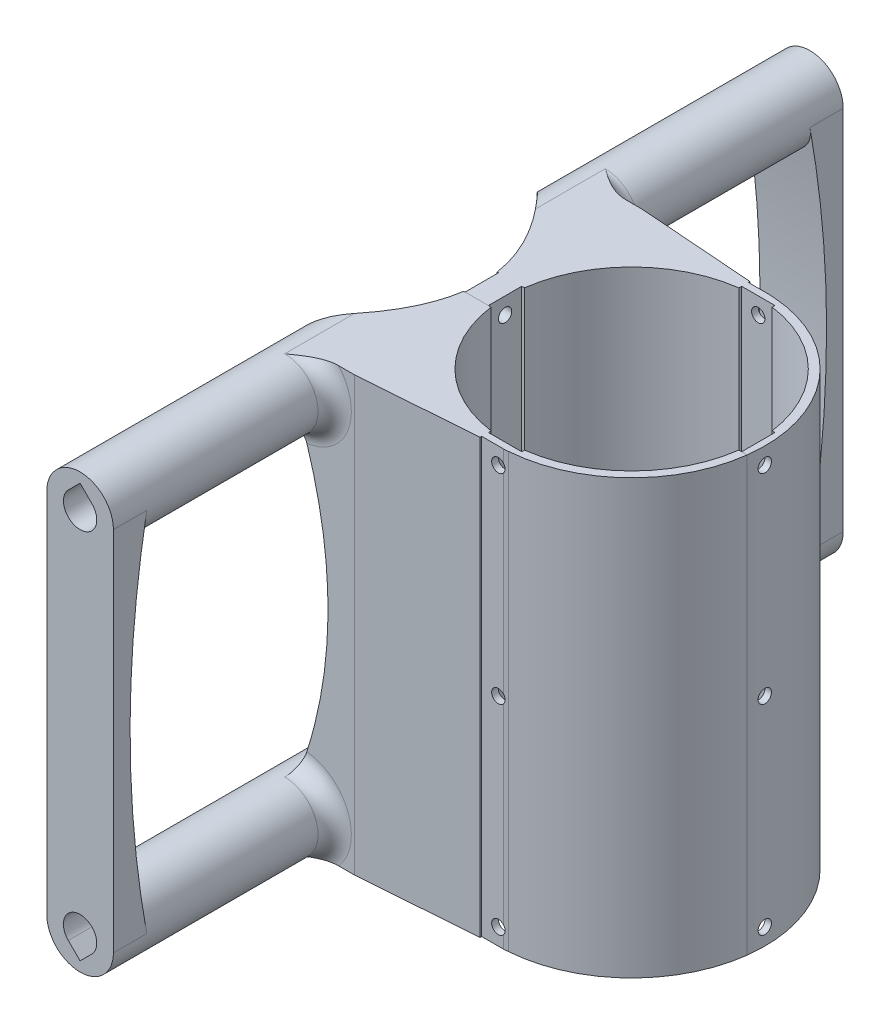
SolidWorks part; units mm, degrees
ref_plane "Front Plane" through (0, 0, 0) normal (0, 0, 1) x (1, 0, 0)
ref_plane "Top Plane" through (0, 0, 0) normal (0, 1, 0) x (1, 0, 0)
ref_plane "Right Plane" through (0, 0, 0) normal (1, 0, 0) x (0, 0, -1)
sketch "Sketch1" plane through (0, 0, 0) normal (0, 0, 1) x (1, 0, 0)
  line L4 (16, -10) -> (16, 10)
  line L5 (16, 100) -> (16, 10)
  line L6 (0, 100) -> (16, 55) construction
  line L7 (0, 120) -> (16, 120)
  line L10 (0, -10) -> (16, -10)
  line L12 (16, 55) -> (0, 10) construction
  line L14 (16, 100) -> (16, 120)
  circle A0 centre (0, 0) radius 4.7625
  circle A1 centre (0, 110) radius 4.7625
  arc A2 (0, 120) -> (0, 100) centre (0, 110) ccw
  arc A3 (0, 10) -> (0, -10) centre (0, 0) ccw
  spline S0 degree 2 poles (0, 100) (16, 55) (0, 10) knots 0 0 0 1 1 1
  point P5 (0, 55)
  dimension "D1" = 110
  dimension "D2" = 90
  dimension "D3" = 9.525
  dimension "D7" = 10
  dimension "D5" = 91.8619
  dimension "D6" = 10
  dimension "D4" = 20
  dimension "D8" = 65
  dimension "D9" = 16
extrude "Boss-Extrude1" add sketch "Sketch1" along normal blind 86.2 contours L4 A1 A0 region at (8, -8.6743, 0)
ref_plane "Plane3" through (0, 55, 0) normal (0, 1, 0) x (1, 0, 0)
sketch "Sketch3" plane through (0, 0, 0) normal (0, 1, 0) x (1, 0, 0)
  line L0 (16, 0) -> (58.9802, -3.2112)
  line L1 (16, -86.2) -> (58.9802, -82.9888)
  line L4 (16, 0) -> (16, -86.2)
  circle A1 centre (56, -43.1) radius 37.5
  arc A2 (58.9802, -82.9888) -> (58.9802, -3.2112) centre (56, -43.1) ccw
  dimension "D1" = 75
  dimension "D2" = 80
  dimension "D4" = 86.2
  dimension "D3" = 40
extrude "Boss-Extrude3" add sketch "Sketch3" along direction (0, 1, 0) on the side of the normal through all and the other way through all
sketch "Sketch9" plane through (0, 0, 86.2) normal (0, 0, 1) x (1, 0, 0)
  circle A0 centre (0, 110) radius 4.7625
  circle A1 centre (0, 110) radius 10
  circle A2 centre (0, 0) radius 10
  circle A3 centre (0, 0) radius 4.7625
  dimension "D1" = 9.525
  dimension "D2" = 20
  dimension "D4" = 110
  dimension "D3" = 2
extrude "Boss-Extrude5" add sketch "Sketch9" along normal blind 66.4 and the other way blind 152.6
sketch "Sketch4" plane through (0, 120, 0) normal (0, 1, 0) x (1, 0, 0)
  line L0 (-10, 66.4) -> (-10, -152.6) construction
  line L5 (-10, -5.6) -> (-10, -80.6)
  circle A2 centre (56, -43.1) radius 37.5 construction
  spline S0 degree 2 poles (-10, -80.6) (32, -43.1) (-10, -5.6) knots 0 0 0 1 1 1
  dimension "D2" = 21
  dimension "D4" = 37.5
  dimension "D3" = 45
  dimension "D1" = 75
extrude "Cut-Extrude1" cut sketch "Sketch4" against normal through all contours L5 S0 | S0 region at (-1.6, 120, 43.1)
ref_point "Point2"
sketch "Sketch7" plane through (0, 120, 0) normal (0, 1, 0) x (1, 0, 0)
  line L0 (51.0254, -81.1) -> (51.0254, -48.1)
  line L1 (51.0254, -81.1) -> (61.0254, -81.1)
  line L2 (51.0254, -5.1) -> (61.0254, -5.1)
  line L3 (61.0254, -81.1) -> (61.0254, -48.1)
  line L4 (51.0254, -81.1) -> (61.0254, -5.1) construction
  line L5 (51.0254, -5.1) -> (61.0254, -81.1) construction
  line L6 (18.0254, -48.1) -> (51.0254, -48.1)
  line L7 (18.0254, -48.1) -> (18.0254, -38.1)
  line L8 (94.0254, -48.1) -> (94.0254, -38.1)
  line L9 (18.0254, -38.1) -> (51.0254, -38.1)
  line L10 (18.0254, -48.1) -> (94.0254, -38.1) construction
  line L11 (94.0254, -48.1) -> (18.0254, -38.1) construction
  line L12 (61.0254, -38.1) -> (61.0254, -5.1)
  line L13 (61.0254, -48.1) -> (94.0254, -48.1)
  line L14 (51.0254, -38.1) -> (51.0254, -5.1)
  line L15 (61.0254, -38.1) -> (94.0254, -38.1)
  line L16 (61.0254, -83.1) -> (51.0254, -83.1)
  line L17 (96.0254, -38.1) -> (106.0254, -38.1)
  line L18 (96.0254, -38.1) -> (96.0254, -48.1)
  line L19 (96.0254, -48.1) -> (106.0254, -48.1)
  line L20 (106.0254, -38.1) -> (106.0254, -48.1)
  line L21 (61.0254, -83.1) -> (61.0254, -93.1)
  line L22 (61.0254, -93.1) -> (51.0254, -93.1)
  line L23 (51.0254, -83.1) -> (51.0254, -93.1)
  line L24 (11.0254, -48.1) -> (11.0254, -38.1)
  line L25 (11.0254, -48.1) -> (1.0254, -48.1)
  line L26 (1.0254, -48.1) -> (1.0254, -38.1)
  line L27 (11.0254, -38.1) -> (1.0254, -38.1)
  line L28 (51.0254, -3.1) -> (61.0254, -3.1)
  line L29 (51.0254, -3.1) -> (51.0254, 6.9)
  line L30 (51.0254, 6.9) -> (61.0254, 6.9)
  line L31 (61.0254, -3.1) -> (61.0254, 6.9)
  point P1 (56.0254, -43.1)
  point P2 (56.0254, -43.1)
  point P33 (56.0254, -43.1)
  dimension "D1" = 10
  dimension "D2" = 38
  dimension "D3" = 76
  dimension "D4" = 2
  dimension "D5" = 10
  dimension "D6" = 10
  dimension "D8" = 7
extrude "Cut-Extrude2" cut sketch "Sketch7" against normal through all
fillet "Fillet4" radius 5 4 edges at (10, 110, 0) (10, 0, 0) (10, 0, 86.2) (10, 110, 86.2)
ref_plane "Plane10" through (-10, 0, 0) normal (-1, 0, 0) x (0, 0, 1)
sketch "Sketch23" plane through (-10, 0, 0) normal (-1, 0, 0) x (0, 0, 1)
  line L0 (152.6, 110) -> (142.6, 110)
  line L1 (152.6, 100) -> (152.6, 120) construction
  line L2 (152.6, 0) -> (142.6, 0)
  line L3 (152.6, -10) -> (152.6, 10) construction
  line L4 (152.6, 110) -> (152.6, 0)
  line L5 (142.6, 110) -> (152.6, 55) construction
  line L6 (152.6, 55) -> (142.6, 0) construction
  spline S1 degree 2 poles (142.6, 110) (152.6, 55) (142.6, 0) knots 0 0 0 1 1 1
  dimension "D1" = 10
  dimension "D2" = 10
extrude "Boss-Extrude9" add sketch "Sketch23" against normal blind 20
ref_plane "Plane11" through (0, 0, 43.1) normal (0, 0, -1) x (-1, 0, 0)
mirror "Mirror1" about plane through (0, 0, 43.1) normal (0, 0, -1) of "Boss-Extrude9"
sketch "Sketch24" plane through (0, 0, -66.4) normal (0, 0, -1) x (-1, 0, 0)
  line L0 (-4.7625, 110) -> (4.7625, 110) construction
  line L1 (-3.5355, 113.5355) -> (0, 117.0711)
  line L2 (0, 117.0711) -> (3.5355, 113.5355)
  line L3 (-3.5355, -3.5355) -> (0, -7.0711)
  line L4 (0, -7.0711) -> (3.5355, -3.5355)
  arc A0 (-3.5355, 113.5355) -> (3.5355, 113.5355) centre (0, 110) ccw
  arc A1 (3.5355, -3.5355) -> (-3.5355, -3.5355) centre (0, 0) ccw
  dimension "D1" = 10
  dimension "D2" = 10
  dimension "D3" = 90
  dimension "D5" = 90
extrude "Cut-Extrude6" cut sketch "Sketch24" against normal through all
sketch "Sketch25" plane through (11.0254, 0, 0) normal (-1, 0, 0) x (0, 0, 1)
  line L0 (43.1, 5.5) -> (43.1, -5.5) construction
  line L1 (48.1, 120) -> (38.1, 120) construction
  circle A0 centre (43.1, 115) radius 2
  circle A1 centre (43.1, 55) radius 2
  circle A2 centre (43.1, -5) radius 2
  dimension "D1" = 4
  dimension "D5" = 60
  dimension "D2" = 5
  dimension "D3" = 3
ref_axis "Axis1" through (56, 120, 43.1) along (0, -1, 0)
extrude "Cut-Extrude7" cut sketch "Sketch25" against normal blind 10 and the other way blind 10
pattern_circular "CirPattern5" count 4 over 360 about axis through (56, 120, 43.1) along (0, -1, 0) of "Cut-Extrude7"
sketch "Sketch26" plane through (11.0254, 0, 0) normal (-1, 0, 0) x (0, 0, 1)
sketch "Sketch27" plane through (0, -10, 0) normal (0, -1, 0) x (1, 0, 0)
  line L0 (10.8705, 0) -> (11.1803, 86.2) construction
  text T0 "FRONT TOWARDS ENEMY" font "Century Gothic" height 5
  point P3 (11.0254, 43.1)
extrude "Boss-Extrude10" add sketch "Sketch27" along normal blind 0.5
sketch "Sketch28" plane through (11.0254, 0, 0) normal (-1, 0, 0) x (0, 0, 1)
  circle A2 centre (51.1, 55) radius 4
  dimension "D1" = 8
extrude "Cut-Extrude9" cut sketch "Sketch28" against normal blind 10 and the other way blind 10
ref_plane "Plane13" through (0, 0, 48.1) normal (0, 0, 1) x (1, 0, 0)
split "Split3" trim tools "Plane13" bodies to split 130 resulting bodies 135 136
